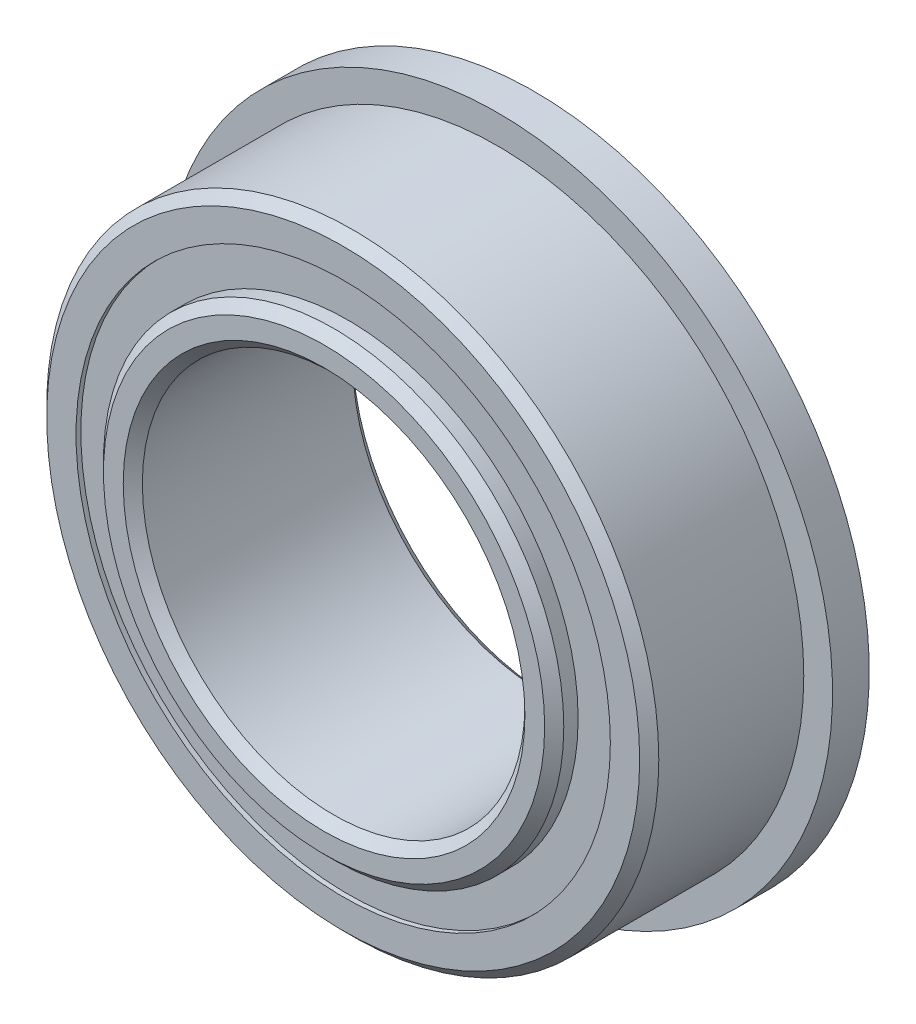
SolidWorks part; units mm, degrees
ref_plane "Front Plane" through (0, 0, 0) normal (0, 0, 1) x (1, 0, 0)
ref_plane "Top Plane" through (0, 0, 0) normal (0, 1, 0) x (1, 0, 0)
ref_plane "Right Plane" through (0, 0, 0) normal (1, 0, 0) x (0, 0, -1)
sketch "Sketch1" plane through (0, 0, 0) normal (1, 0, 0) x (0, 0, -1)
  line L0 (-1.9844, 0) -> (1.9844, 0) construction
  line L1 (0, 6.35) -> (0, -6.35) construction
  line L2 (1.7859, 6.35) -> (-1.7859, 6.35)
  line L3 (-1.7859, 6.35) -> (-1.9844, 6.1516)
  line L4 (-1.9844, 6.1516) -> (-1.9844, 5.5432)
  line L5 (-1.9844, 5.5432) -> (-0.8819, 5.5432)
  line L6 (1.9844, 5.5432) -> (0.8819, 5.5432)
  line L7 (1.9844, 6.1516) -> (1.9844, 5.5432)
  line L8 (1.7859, 6.35) -> (1.9844, 6.1516)
  line L9 (0, 6.35) -> (0, 5.1594) construction
  line L10 (0, 5.1594) -> (0, 3.9688) construction
  arc A0 (-0.8819, 5.5432) -> (0.8819, 5.5432) centre (0, 5.1594) cw
  point P14 (0, 3.9688)
  dimension "Width" = 3.9688
  dimension "OD" = 12.7
  dimension "D1" = 45
  dimension "D2" = 0.1984
  dimension "D3" = 1.7639
  dimension "D4" = 0.3838
revolve "Revolve1" add sketch "Sketch1" angle 360 about L0
sketch "Sketch3" plane through (0, 0, 0) normal (1, 0, 0) x (0, 0, -1)
  line L0 (-0.8819, 4.7756) -> (-2.3813, 4.7756) construction
  line L1 (-1.9844, 6.1516) -> (-1.9844, 5.5432) construction
  line L2 (-1.7859, 6.35) -> (-1.9844, 6.1516) construction
  line L3 (-2.3813, 4.7756) -> (-2.3813, 4.1672) construction
  line L4 (-2.3813, 4.1672) -> (-2.3813, 4.5771)
  line L5 (-2.3813, 4.1672) -> (-2.1828, 3.9688)
  line L6 (-2.1828, 3.9688) -> (2.1828, 3.9688)
  line L8 (2.1828, 3.9688) -> (2.3812, 4.1672)
  line L10 (2.3812, 4.1672) -> (2.3813, 4.7756) construction
  line L11 (2.3813, 4.7756) -> (0.8819, 4.7756) construction
  line L12 (0, 6.35) -> (0, -6.35) construction
  line L13 (1.7859, 6.35) -> (1.9844, 6.1516) construction
  line L14 (-2.3813, 4.5771) -> (-2.1828, 4.7756)
  line L15 (-2.1828, 4.7756) -> (-0.8819, 4.7756)
  line L16 (0.8819, 4.7756) -> (2.1828, 4.7756)
  line L17 (2.1828, 4.7756) -> (2.3813, 4.5771)
  line L18 (2.3813, 4.5771) -> (2.3812, 4.1672)
  arc A1 (0.8819, 4.7756) -> (-0.8819, 4.7756) centre (0, 5.1594) cw
  arc A2 (0.8819, 5.5432) -> (-0.8819, 5.5432) centre (0, 5.1594) ccw construction
  dimension "D1" = 45
  dimension "Ring Wd" = 4.7625
revolve "Revolve3" add sketch "Sketch3" angle 360 about L0
sketch "Sketch4" plane through (0, 0, 0) normal (1, 0, 0) x (0, 0, -1)
  line L0 (-0.9618, 5.1594) -> (0.9618, 5.1594)
  arc A2 (-0.9618, 5.1594) -> (0.9618, 5.1594) centre (0, 5.1594) cw
  arc A3 (0.8819, 5.5432) -> (-0.8819, 5.5432) centre (0, 5.1594) ccw construction
revolve "Revolve4" add sketch "Sketch4" angle 360 about L0
ref_axis "Axis1" through (0, 0, -1.9844) along (0, 0, 1)
pattern_circular "CirPattern1" count 12 every 30 about axis through (0, 0, -1.9844) along (0, 0, 1) of bodies 104
sketch "Sketch5" plane through (0, 0, 0) normal (1, 0, 0) x (0, 0, -1)
  line L0 (-1.9844, 5.5432) -> (-0.8819, 5.5432) construction
  line L1 (-1.8852, 5.5432) -> (-0.9618, 5.5432)
  line L2 (-1.8852, 5.5432) -> (-1.8852, 4.7756)
  line L3 (-1.8852, 4.7756) -> (-0.9618, 4.7756)
  line L4 (-0.9618, 5.5432) -> (-0.9618, 4.7756)
  line L5 (-0.8819, 4.7756) -> (-2.3813, 4.7756) construction
  line L6 (1.9844, 5.5432) -> (0.8819, 5.5432) construction
  line L7 (1.8852, 5.5432) -> (0.9618, 5.5432)
  line L8 (1.8852, 5.5432) -> (1.8852, 4.7756)
  line L9 (1.8852, 4.7756) -> (0.9618, 4.7756)
  line L10 (0.9618, 5.5432) -> (0.9618, 4.7756)
  line L11 (2.3813, 4.7756) -> (0.8819, 4.7756) construction
  line L12 (-1.7859, 6.35) -> (-1.9844, 6.1516) construction
  point P18 (-1.8852, 6.2508)
revolve "Revolve5" add sketch "Sketch5" angle 360 about L0
sketch "Sketch6" plane through (0, 0, 0) normal (1, 0, 0) x (0, 0, -1)
  line L1 (1.9844, 5.5432) -> (1.2224, 5.5432)
  line L2 (1.9844, 5.5432) -> (1.9844, 6.9469)
  line L3 (1.9844, 6.9469) -> (1.2224, 6.9469)
  line L4 (1.2224, 5.5432) -> (1.2224, 6.9469)
  line L5 (1.9844, 0) -> (-1.9844, 0) construction
  dimension "Flange OD" = 13.8938
  dimension "Th" = 0.762
revolve "Revolve6" add sketch "Sketch6" angle 360 about L5
equation "\"D2@Sketch1\" = \"Width@Sketch1\"*.05"
equation "\"D3@Sketch1\" = \"Width@Sketch1\"/2.25"
equation "\"D4@Sketch1\" = (((\"OD@Sketch1\"-\"Width@Sketch1\")/2)/3.25)/3.5"
equation "\"D2@CirPattern1\" = 360/\"Balls@CirPattern1\""
